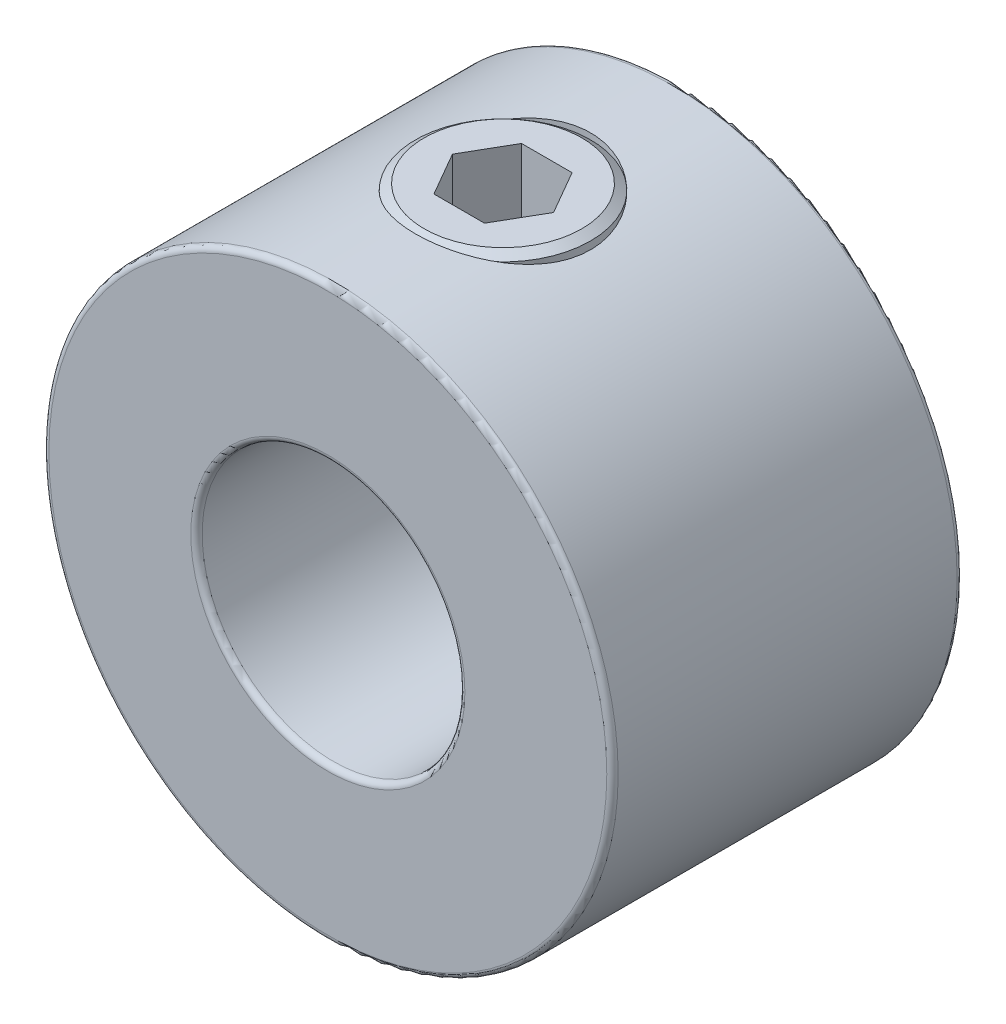
SolidWorks part; units mm, degrees
ref_plane "Front Plane" through (0, 0, 0) normal (0, 0, 1) x (1, 0, 0)
ref_plane "Top Plane" through (0, 0, 0) normal (0, 1, 0) x (1, 0, 0)
ref_plane "Right Plane" through (0, 0, 0) normal (1, 0, 0) x (0, 0, -1)
sketch "Sketch1" plane through (0, 0, 0) normal (0, 0, 1) x (1, 0, 0)
  circle A0 centre (0, 0) radius 6.5
  circle A1 centre (0, 0) radius 3
  point P4 (6.5, 0)
  point P5 (0, 6.5)
  dimension "Bore Dia" = 6
  dimension "OD" = 13
extrude "Extrude1" add sketch "Sketch1" along normal blind 8
ref_plane "Plane1" through (0, 6.5, 0) normal (0, 1, 0) x (-1, 0, 0)
sketch "Sketch2" plane through (0, 6.5, 0) normal (0, 1, 0) x (-1, 0, 0)
  line L0 (0, 0) -> (0, 8) construction
  line L2 (6.5, 8) -> (-6.5, 8) construction
  circle A0 centre (0, 4) radius 2
  dimension "Set Screw Dia" = 4
extrude "Cut-Extrude1" cut sketch "Sketch2" against normal up to surface (6.5 mm away) up to plane "Top Plane"
ref_plane "Plane2" through (0, 0, 4) normal (0, 0, 1) x (1, 0, 0)
sketch "Sketch3" plane through (0, 0, 4) normal (0, 0, 1) x (1, 0, 0)
  line L0 (-1.8, 6.5) -> (-2, 6.36)
  line L1 (0, 3.1585) -> (0, 6.5)
  line L3 (-2, 3.4041) -> (-2, 6.36)
  line L4 (0, 6.5) -> (-1.8, 6.5)
  line L5 (0, 2.5) -> (0, 0) construction
  line L6 (-2, 6.36) -> (0, 6.36) construction
  line L7 (0, 3.1585) -> (-1.0959, 2.5)
  line L8 (-1.0959, 2.5) -> (-2, 3.4041)
  point P1 (-1.0959, 2.5)
  dimension "Screw Length" = 4
  dimension "D3" = 4
  dimension "D1" = 3.6
  dimension "D7" = 2
  dimension "D2" = 35
  dimension "D4" = 59
  dimension "D5" = 45
revolve "Revolve1" add sketch "Sketch3" angle 360 about L1
sketch "Sketch4" plane through (0, 6.5, 0) normal (0, 1, 0) x (0, 0, -1)
  line L0 (-4, 1.1547) -> (-4, -1.1547) construction
  line L1 (-4, 1.1547) -> (-5, 0.5774)
  line L2 (-5, 0.5774) -> (-5, -0.5774)
  line L3 (-5, -0.5774) -> (-4, -1.1547)
  line L4 (-4, -1.1547) -> (-3, -0.5774)
  line L5 (-3, -0.5774) -> (-3, 0.5774)
  line L6 (-3, 0.5774) -> (-4, 1.1547)
  circle A0 centre (-4, 0) radius 1 construction
  circle A1 centre (-4, 0) radius 1.1547 construction
  dimension "D1" = 2.3094
  dimension "Hex" = 2
extrude "Cut-Extrude2" cut sketch "Sketch4" against normal blind 1.6
fillet "Fillet1" radius 0.13 4 edges at (3, 0, 0) (3, 0, 8) (6.5, 0, 0) (6.5, 0, 8)
ref_plane "Contact Plane 1" through (0, 0, 8) normal (0, 0, 1) x (1, 0, 0)
ref_plane "Contact Plane 2" through (0, 0, 0) normal (0, 0, -1) x (-1, 0, 0)
ref_plane "Contact Plane 3" through (0, 2.5, 0) normal (0, -1, 0) x (-1, 0, 0)
ref_axis "Central Axis 1" through (0, 0, 7.87) along (0, 0, -1)
equation "\"D1@Fillet1\" = \"OD@Sketch1\"*.01"
equation "\"D1@Cut-Extrude2\" = \"Hex@Sketch4\"*.8"
equation "\"D3@Sketch3\"=\"Set Screw Dia@Sketch2\""
equation "\"D1@Sketch3\"=\"Set Screw Dia@Sketch2\"*.9"
